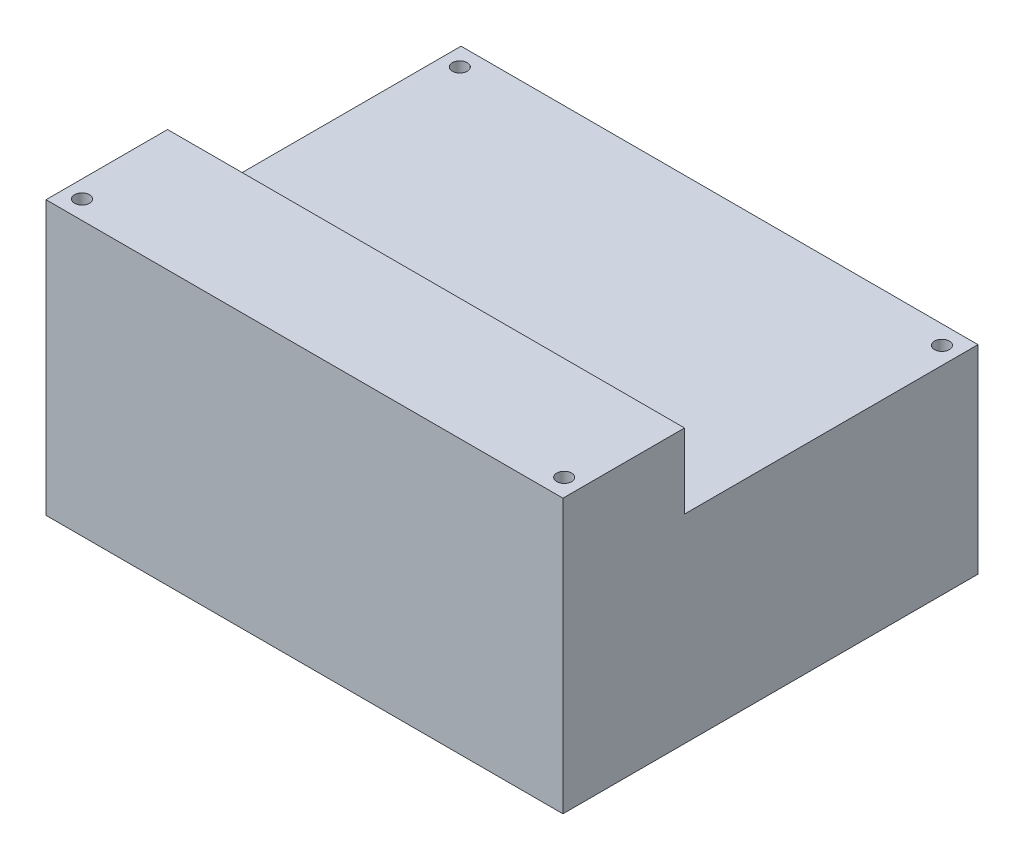
SolidWorks part; units mm, degrees
ref_plane "Front Plane" through (0, 0, 0) normal (0, 0, 1) x (1, 0, 0)
ref_plane "Top Plane" through (0, 0, 0) normal (0, 1, 0) x (1, 0, 0)
ref_plane "Right Plane" through (0, 0, 0) normal (1, 0, 0) x (0, 0, -1)
sketch "Sketch1" plane through (0, 0, 0) normal (0, 1, 0) x (1, 0, 0)
  line L1 (0, 0) -> (104, 0)
  line L2 (0, 0) -> (0, 83.5)
  line L3 (0, 83.5) -> (104, 83.5)
  line L4 (104, 0) -> (104, 83.5)
  dimension "D1" = 104
  dimension "D2" = 83.5
extrude "Boss-Extrude1" add sketch "Sketch1" along normal blind 55
sketch "Sketch2" plane through (104, 0, 0) normal (1, 0, 0) x (0, 0, -1)
  line L0 (0, 0) -> (83.5, 0) construction
  line L1 (83.5, 55) -> (24.4578, 55)
  line L2 (83.5, 55) -> (83.5, 40)
  line L3 (83.5, 40) -> (24.4578, 40)
  line L4 (24.4578, 55) -> (24.4578, 40)
  dimension "D1" = 40
extrude "Cut-Extrude1" cut sketch "Sketch2" against normal through all
sketch "Sketch3" plane through (0, 0, 0) normal (0, -1, 0) x (1, 0, 0)
  line L0 (0, -83.5) -> (104, 0) construction
  line L2 (100.5, -3.75) -> (3.5, -3.75) construction
  line L3 (100.5, -3.75) -> (100.5, -79.75) construction
  line L4 (0, 0) -> (0, -83.5)
  line L5 (0, -83.5) -> (104, -83.5)
  line L6 (104, -83.5) -> (104, 0)
  line L7 (104, 0) -> (0, 0)
  line L8 (0, 0) -> (0, -83.5) construction
  line L9 (0, -83.5) -> (104, -83.5) construction
  line L10 (104, -83.5) -> (104, 0) construction
  line L11 (104, 0) -> (0, 0) construction
  line L12 (100.5, -79.75) -> (3.5, -79.75) construction
  line L13 (3.5, -3.75) -> (3.5, -79.75) construction
  line L14 (100.5, -3.75) -> (3.5, -79.75) construction
  line L15 (100.5, -79.75) -> (3.5, -3.75) construction
  circle A0 centre (3.5, -79.75) radius 1.5
  circle A1 centre (3.5, -3.75) radius 1.5
  circle A2 centre (100.5, -3.75) radius 1.5
  circle A3 centre (100.5, -79.75) radius 1.5
  point P2 (52, -41.75)
  dimension "D3" = 3
  dimension "D2" = 97
  dimension "D4" = 76
  dimension "D1" = 0
extrude "Cut-Extrude2" cut sketch "Sketch3" against normal through all
